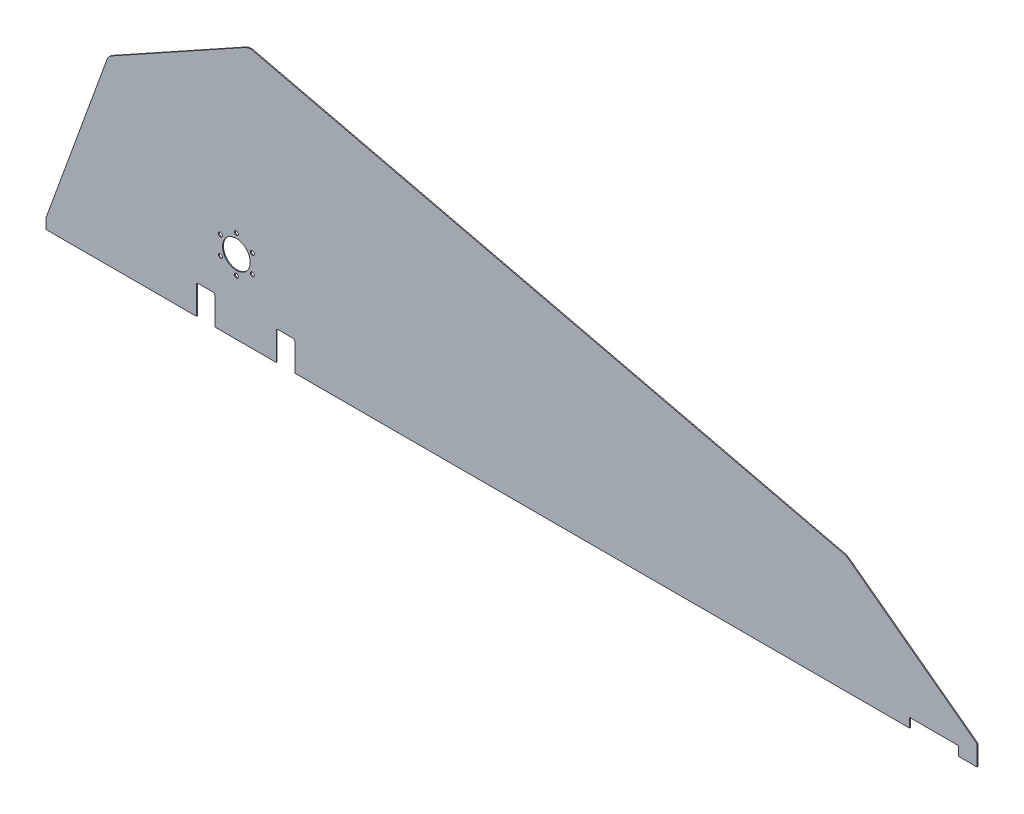
SolidWorks part; units mm, degrees
material "AISI 1020"
ref_plane "Спереди" through (0, 0, 0) normal (0, 0, 1) x (1, 0, 0)
ref_plane "Сверху" through (0, 0, 0) normal (0, 1, 0) x (1, 0, 0)
ref_plane "Справа" through (0, 0, 0) normal (1, 0, 0) x (0, 0, -1)
sketch "Эскиз1" plane through (0, 0, 0) normal (0, 0, 1) x (1, 0, 0)
  line L0 (677.2668, -1.5) -> (677.2668, -16.5) construction
  line L1 (677.2668, -1.5) -> (677.2668, -16.5)
  line L2 (757.2668, -16.5) -> (757.2668, -1.5) construction
  line L3 (757.2668, -16.5) -> (757.2668, -1.5)
  line L4 (757.2668, -1.5) -> (677.2668, -1.5) construction
  line L5 (757.2668, -1.5) -> (677.2668, -1.5)
  line L6 (-390.9514, 403.6815) -> (571.018, 175.4665) construction
  line L7 (577.3384, 172.5171) -> (643.3256, 123.3551) construction
  line L8 (-390.9514, 403.6815) -> (571.018, 175.4665)
  line L9 (577.3384, 172.5171) -> (643.3256, 123.3551)
  line L10 (-620.4325, 281.5667) -> (-403.292, 401.9839) construction
  line L11 (-620.4325, 281.5667) -> (-403.292, 401.9839)
  line L12 (-665.6077, 169.8068) -> (-628.2718, 272.3862) construction
  line L13 (-665.6077, 169.8068) -> (-628.2718, 272.3862)
  line L14 (-665.6077, 169.8068) -> (-727.4123, 0)
  line L15 (-732.7332, 0) -> (817.2668, 0) construction
  line L16 (-727.4123, 0) -> (-727.4123, -16.5)
  line L17 (-727.4123, -16.5) -> (-482.7332, -16.5)
  line L18 (643.3256, 123.3551) -> (787.2668, 16.1156)
  line L19 (787.2668, 16.1156) -> (787.2668, -16.5)
  line L20 (787.2668, -16.5) -> (757.2668, -16.5)
  line L21 (-452.7332, 4.2262) -> (-452.7332, 28.2262) construction
  line L23 (-482.7332, 28.2262) -> (-482.7332, 4.2262) construction
  line L24 (-455.7332, 31.2262) -> (-479.7332, 31.2262) construction
  line L25 (-452.7332, 4.2262) -> (-452.7332, 28.2262)
  line L27 (-482.7332, 28.2262) -> (-482.7332, 4.2262)
  line L28 (-455.7332, 31.2262) -> (-479.7332, 31.2262)
  line L29 (-322.7332, 4.2262) -> (-322.7332, 28.2262) construction
  line L31 (-352.7332, 28.2262) -> (-352.7332, 4.2262) construction
  line L32 (-325.7332, 31.2262) -> (-349.7332, 31.2262) construction
  line L33 (-322.7332, 4.2262) -> (-322.7332, 28.2262)
  line L35 (-352.7332, 28.2262) -> (-352.7332, 4.2262)
  line L36 (-325.7332, 31.2262) -> (-349.7332, 31.2262)
  line L37 (-417.7332, 103.2262) -> (-417.7332, 133.2262) construction
  line L38 (-417.7332, 103.2262) -> (-417.7332, 133.2262) construction
  line L39 (-482.7332, 4.2262) -> (-482.7332, -16.5)
  line L41 (-452.7332, -16.5) -> (-452.7332, 4.2262)
  line L43 (-352.7332, 4.2262) -> (-352.7332, -16.5)
  line L45 (-322.7332, -16.5) -> (-322.7332, 4.2262)
  line L46 (-322.7332, -16.5) -> (677.2668, -16.5)
  line L47 (-452.7332, -16.5) -> (-352.7332, -16.5)
  arc A0 (577.3384, 172.5171) -> (571.018, 175.4665) centre (567.0385, 158.6921) ccw construction
  arc A1 (577.3384, 172.5171) -> (571.018, 175.4665) centre (567.0385, 158.6921) ccw
  arc A2 (-390.9514, 403.6815) -> (-403.292, 401.9839) centre (-394.931, 386.9071) ccw construction
  arc A3 (-390.9514, 403.6815) -> (-403.292, 401.9839) centre (-394.931, 386.9071) ccw
  arc A4 (-620.4325, 281.5667) -> (-628.2718, 272.3862) centre (-612.0715, 266.4898) ccw construction
  arc A5 (-620.4325, 281.5667) -> (-628.2718, 272.3862) centre (-612.0715, 266.4898) ccw
  arc A6 (-452.7332, 28.2262) -> (-455.7332, 31.2262) centre (-455.7332, 28.2262) ccw construction
  arc A9 (-479.7332, 31.2262) -> (-482.7332, 28.2262) centre (-479.7332, 28.2262) ccw construction
  arc A10 (-452.7332, 28.2262) -> (-455.7332, 31.2262) centre (-455.7332, 28.2262) ccw
  arc A13 (-479.7332, 31.2262) -> (-482.7332, 28.2262) centre (-479.7332, 28.2262) ccw
  arc A14 (-322.7332, 28.2262) -> (-325.7332, 31.2262) centre (-325.7332, 28.2262) ccw construction
  arc A17 (-349.7332, 31.2262) -> (-352.7332, 28.2262) centre (-349.7332, 28.2262) ccw construction
  arc A18 (-322.7332, 28.2262) -> (-325.7332, 31.2262) centre (-325.7332, 28.2262) ccw
  arc A21 (-349.7332, 31.2262) -> (-352.7332, 28.2262) centre (-349.7332, 28.2262) ccw
  circle A23 centre (-417.7332, 133.2262) radius 3.25
  circle A24 centre (-417.7332, 103.2262) radius 22.5
  circle A25 centre (-417.7332, 103.2262) radius 22.5
  circle A26 centre (-391.7524, 118.2262) radius 3.25
  circle A27 centre (-391.7524, 88.2262) radius 3.25
  circle A28 centre (-417.7332, 73.2262) radius 3.25
  circle A29 centre (-443.714, 88.2262) radius 3.25
  circle A30 centre (-443.714, 118.2262) radius 3.25
  point P62 (-417.7332, 103.2262)
  dimension "D4" = 6.5
  dimension "D1" = 30
  dimension "D3" = 30
  dimension "D6" = 30
  dimension "D2" = 10
  dimension "D5" = 6
base flange "Базовая кромка1" sketch "Эскиз1" thickness 1.5 reverse thickness direction yes parameters "D1"=0.74
sketch "Сгиб-Линии1" [suppressed] plane through (0, 0, 0) normal (0, 1, 0) x (1, 0, 0)
sketch "Граничная рамка1" [suppressed] plane through (0, 0, 0) normal (0, 1, 0) x (1, 0, 0)
sheet metal parameters "Листовой металл3" thickness 1.5 parameters "D1"=0.74
flat pattern "Развертка3" [suppressed]
sketch "Сгиб-Линии2" plane through (0, 0, 0) normal (0, 1, 0) x (1, 0, 0)
sketch3d "Граничная рамка2" [suppressed]
  line L0 (401.6791, 375.9209, 0) -> (-1113, 375.9209, 0) construction
  line L1 (401.6791, -44.7261, 0) -> (-1113, -44.7262, 0) construction
  line L2 (401.6791, 375.9209, 0) -> (401.6791, -44.7261, 0) construction
  line L3 (-1113, 375.9209, 0) -> (-1113, -44.7262, 0) construction
